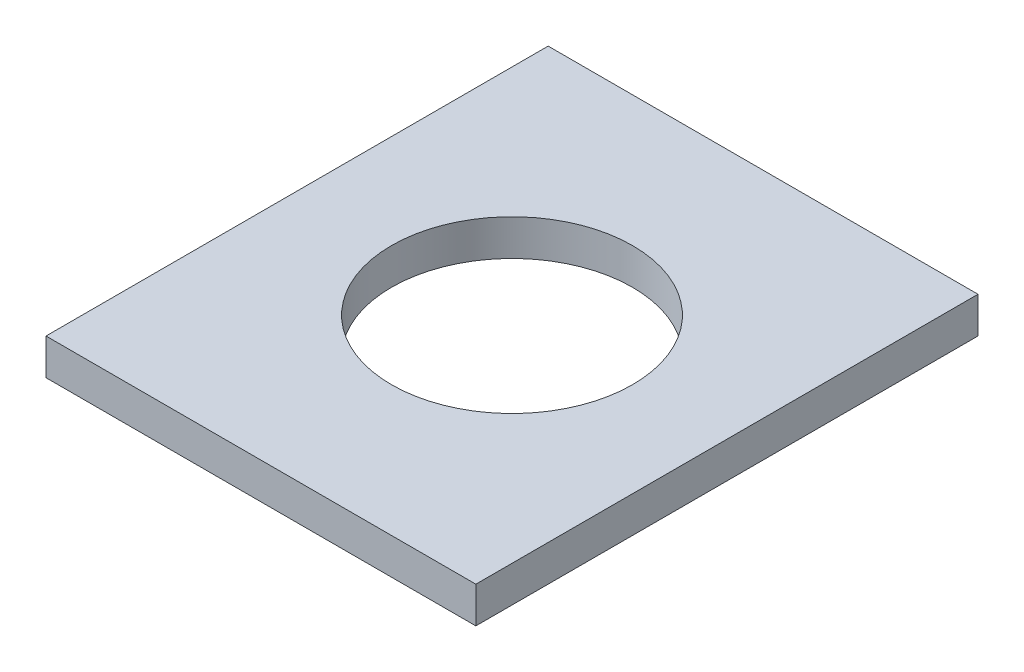
SolidWorks part; units mm, degrees
ref_plane "前视基准面" through (0, 0, 0) normal (0, 0, 1) x (1, 0, 0)
ref_plane "上视基准面" through (0, 0, 0) normal (0, 1, 0) x (1, 0, 0)
ref_plane "右视基准面" through (0, 0, 0) normal (1, 0, 0) x (0, 0, -1)
other "Configuration Table"
sketch "草图1" plane through (0, 0, 0) normal (0, 1, 0) x (1, 0, 0)
  line L1 (-107, -125) -> (107, -125)
  line L2 (-107, -125) -> (-107, 125)
  line L3 (-107, 125) -> (107, 125)
  line L4 (107, -125) -> (107, 125)
  circle A0 centre (0, 0) radius 60
  point P4 (-107, 0)
  point P6 (0, 125)
  dimension "D3" = 120
  dimension "D1" = 250
  dimension "D2" = 214
extrude "凸台-拉伸1" add sketch "草图1" along normal blind 18
